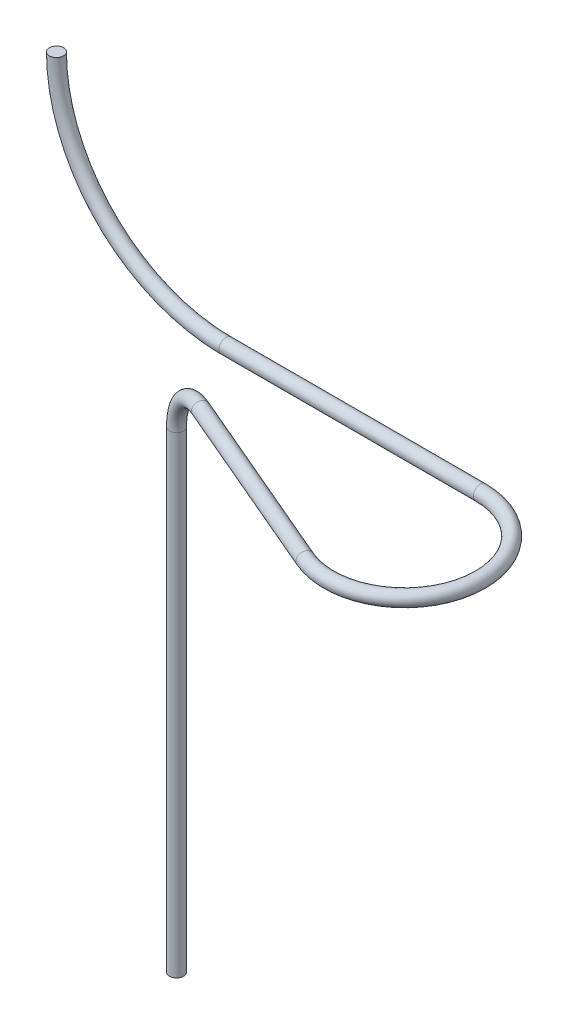
SolidWorks part; units mm, degrees
note: '?' marks a value the reader was unsure of.
ref_plane "prox_pulley" through (0, 0, 0) normal (0, 0, 1) x (1, 0, 0)
ref_plane "Top Plane" through (0, 0, 0) normal (0, 1, 0) x (1, 0, 0)
ref_plane "Right Plane" through (0, 0, 0) normal (1, 0, 0) x (0, 0, -1)
sketch "Sketch1" plane through (0, 0, 0) normal (0, 0, 1) x (1, 0, 0)
  line L0 (0, -12) -> (18, -12)
  circle A0 centre (0, 0) radius 12 construction
  arc A1 (-12, 0) -> (0, -12) centre (0, 0) ccw
  dimension "D1" = 24
  dimension "D2" = 18
ref_plane "trans_pulley" through (0, -12, 0) normal (0, 1, 0) x (1, 0, 0)
ref_plane "lower_pulley_center" through (0, -48.67, 0) normal (0, 1, 0) x (1, 0, 0)
ref_axis "pulley_tangent" through (18, -31.834, 0) along (0, 1, 0)?
sketch "Sketch3" plane through (0, -12, 0) normal (0, 1, 0) x (1, 0, 0)
  line L0 (0, 0) -> (18, 0) construction
  line L1 (0, -6.446) -> (0, 6.446) construction
  line L2 (-12, 0) -> (0, 0) construction
  line L3 (0, -3.5) -> (28.6347, -15.731) construction
  line L4 (15.8946, -10.2892) -> (0, -3.5) construction
  line L5 (15.8946, -10.2892) -> (2.9888, -4.7766)
  circle A0 centre (18, -5.36) radius 5.36 construction
  arc A1 (15.8946, -10.2892) -> (18, 0) centre (18, -5.36) ccw
  point P12 (0, -3.5)
  dimension "D1" = 10.72
  dimension "D2" = 3.5
  dimension "D3" = 3.25
ref_plane "shaft" through (-1.2643, 0, 2.96) normal (-0.3928, 0, 0.9196) x (0.9196, 0, 0.3928)
sketch "Sketch4" plane through (-1.2643, 0, 2.96) normal (-0.3928, 0, 0.9196) x (0.9196, 0, 0.3928)
  line L0 (16.5, -48.67) -> (-16.5, -48.67) construction
  line L3 (1.3748, -15.25) -> (1.3748, -48.67)
  line L4 (0, -12) -> (16.5532, -12) construction
  line L5 (1.3748, -12) -> (5.207, -12) construction
  line L6 (1.3748, -12) -> (1.3748, -16.4947) construction
  circle A0 centre (4.6248, -15.25) radius 3.25 construction
  arc A1 (1.3748, -15.25) -> (4.6248, -12) centre (4.6248, -15.25) cw
  dimension "D1" = 6.5
ref_point "tendon_start"
sketch "Sketch6" plane through (0, 0, 0) normal (0, 1, 0) x (1, 0, 0)
  circle A0 centre (-12, 0) radius 0.5
  dimension "D1" = 1
curve "CompCurve1"
sweep "Sweep1" add profiles "Sketch6" path "CompCurve1"
equation "\"d_horizontal_pulley\"= 6.5"
equation "\"D1@Sketch4\"=\"d_horizontal_pulley\""
equation "\"D3@Sketch3\"=\"d_horizontal_pulley\"/2"
